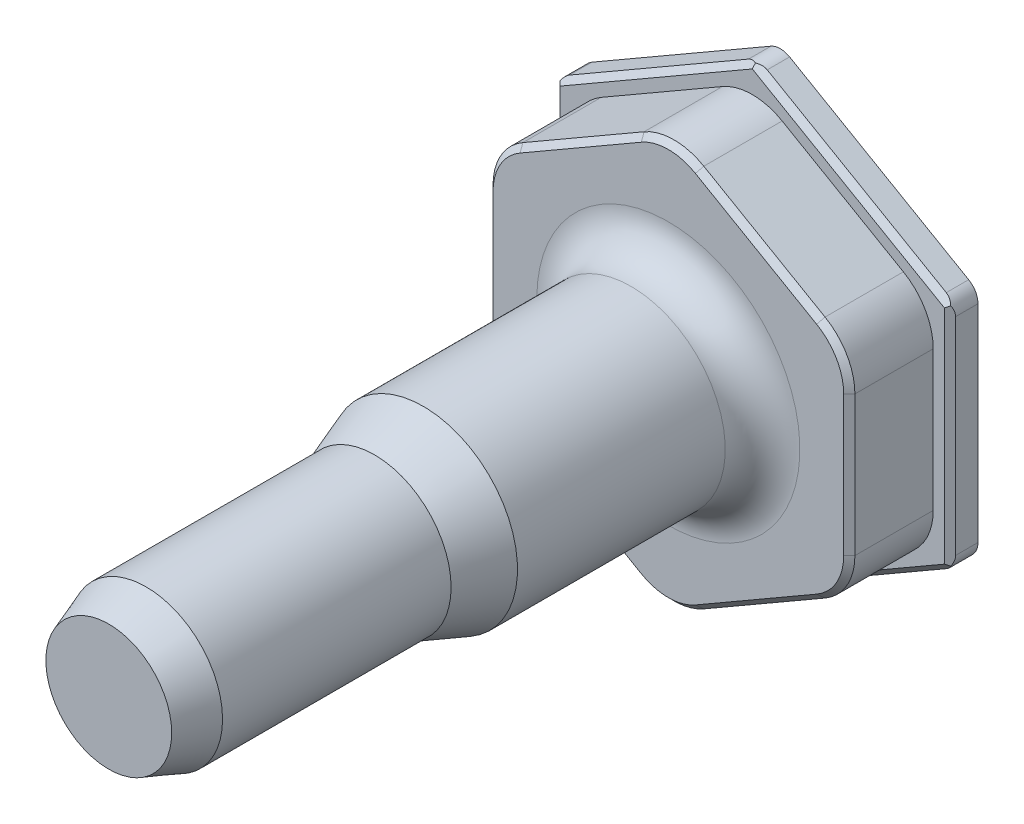
SolidWorks part; units mm, degrees
ref_plane "Front Plane" through (0, 0, 0) normal (0, 0, 1) x (1, 0, 0)
ref_plane "Top Plane" through (0, 0, 0) normal (0, 1, 0) x (1, 0, 0)
ref_plane "Right Plane" through (0, 0, 0) normal (1, 0, 0) x (0, 0, -1)
sketch "Sketch1" plane through (0, 0, 0) normal (0, 0, 1) x (1, 0, 0)
  line L12 (0, 11.2006) -> (9.7, 5.6003)
  line L14 (9.7, 5.6003) -> (9.7, -5.6003)
  line L15 (9.7, -5.6003) -> (0, -11.2006)
  line L16 (0, -11.2006) -> (-9.7, -5.6003)
  line L17 (-9.7, -5.6003) -> (-9.7, 5.6003)
  line L18 (-9.7, 5.6003) -> (0, 11.2006)
  line L19 (-10.6, 6.1199) -> (0, 12.2398)
  line L20 (0, 12.2398) -> (10.6, 6.1199)
  line L21 (10.6, 6.1199) -> (10.6, -6.1199)
  line L22 (10.6, -6.1199) -> (0, -12.2398)
  line L23 (0, -12.2398) -> (-10.6, -6.1199)
  line L24 (-10.6, -6.1199) -> (-10.6, 6.1199)
  circle A1 centre (0, 0) radius 3.25
  circle A2 centre (0, 0) radius 5.05
  circle A3 centre (0, 0) radius 2.125
  circle A4 centre (0, 0) radius 4.1
  point P3 (0, 11.2006)
  point P4 (9.7, 5.6003)
  point P7 (9.7, -5.6003)
  point P9 (0, -11.2006)
  point P10 (-9.7, -5.6003)
  point P12 (-9.7, 5.6003)
  point P13 (0, 0)
  dimension "D1" = 19.4
  dimension "D6" = 6.5
  dimension "D7" = 10.1
  dimension "D8" = 4.25
  dimension "D9" = 8.2
  dimension "D2" = 6
  dimension "D3" = 120
  dimension "D4" = 120
  dimension "D5" = 0.9
extrude "Boss-Extrude1" add sketch "Sketch1" along normal blind 1.5 contours L19 L20 L21 L22 L23 L24
ref_plane "Plane1" through (-10.6, -6.1199, 0) normal (-0.866, 0.5, 0) x (0, 0, 1)
ref_plane "Plane2" through (0, -12.2398, 0) normal (-0.866, 0.5, 0) x (0, 0, 1)
extrude "Boss-Extrude3" add sketch "Sketch1<8>" along normal blind 36 contours A4
sketch "Sketch1<8>" plane through (0, 0, 0) normal (0, 0, 1) x (1, 0, 0) same geometry as "Sketch1"
extrude "Boss-Extrude4" add sketch "Sketch1<9>" along normal blind 19 contours A2
sketch "Sketch1<9>" plane through (0, 0, 0) normal (0, 0, 1) x (1, 0, 0) same geometry as "Sketch1"
shell "Shell1" thickness 2
extrude "Cut-Extrude1" cut sketch "Sketch1<10>" along normal blind 17 contours A1
sketch "Sketch1<10>" plane through (0, 0, 0) normal (0, 0, 1) x (1, 0, 0) same geometry as "Sketch1"
extrude "Boss-Extrude2" add sketch "Sketch1<3>" along normal blind 6 contours L17 L18 L12 L14 L15 L16 | A1
sketch "Sketch1<3>" plane through (0, 0, 0) normal (0, 0, 1) x (1, 0, 0) same geometry as "Sketch1"
chamfer "Chamfer1" distance 2 angle 20 1 edges at (4.1, 0, 36) first distance on face at (4.1, 0, 19)
chamfer "Chamfer2" distance 1 angle 70 1 edges at (4.1, 0, 19) first distance on face at (4.1, 0, 19)
chamfer "Chamfer3" distance 0.7 angle 60 1 edges at (2.1, 0, 17) first distance on face at (2.1, 0, 17)
chamfer "Chamfer6" distance 0.3 angle 45 1 edges at (3.25, 0, 0)
ref_plane "Plane3" through (0, 0, 5) normal (0, 0, 1) x (1, 0, 0)
sketch "Sketch2" plane through (0, 0, 5) normal (0, 0, 1) x (1, 0, 0)
  line L1 (-17.7118, 13.112) -> (21.871, 13.112)
  line L2 (-17.7118, 13.112) -> (-17.7118, -17.4474)
  line L3 (-17.7118, -17.4474) -> (21.871, -17.4474)
  line L4 (21.871, 13.112) -> (21.871, -17.4474)
fillet "Fillet1" radius 3.2 6 edges at (9.7, -5.6003, 3.75) (0, -11.2006, 3.75) (-9.7, -5.6003, 3.75) (-9.7, 5.6003, 3.75) (0, 11.2006, 3.75) (9.7, 5.6003, 3.75)
chamfer "Chamfer5" distance 0.3 angle 45 18 edges at (-9.7, 0, 6) (-4.85, 8.4004, 6) (4.85, 8.4004, 6) (9.7, 0, 6) (4.85, -8.4004, 6) (-4.85, -8.4004, 6) (10.6, 0, 1.5) (5.3, -9.1799, 1.5) (-5.3, -9.1799, 1.5) (-10.6, 0, 1.5) (5.3, 9.1799, 1.5) (-5.3, 9.1799, 1.5) (0, -10.7056, 6) (-9.2713, -5.3528, 6) (-9.2713, 5.3528, 6) (0, 10.7056, 6) (9.2713, 5.3528, 6) (9.2713, -5.3528, 6)
fillet "Fillet2" radius 1 6 edges at (10.6, -6.1199, 0.6) (10.6, 6.1199, 0.6) (0, 12.2398, 0.6) (0, -12.2398, 0.6) (-10.6, -6.1199, 0.6) (-10.6, 6.1199, 0.6)
fillet "Fillet3" radius 2 1 edges at (-5.05, 0, 6)
